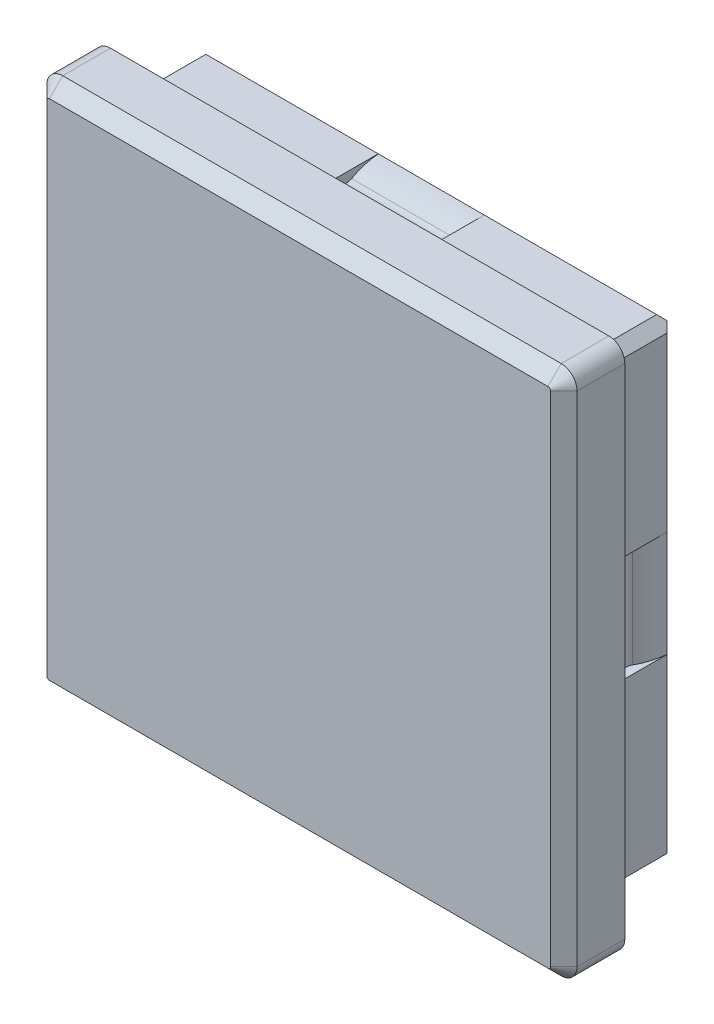
SolidWorks part; units mm, degrees
ref_plane "Front Plane" through (0, 0, 0) normal (1, 0, 0) x (0, 1, 0)
ref_plane "Top Plane" through (0, 0, 0) normal (0, 0, 1) x (0, 1, 0)
ref_plane "Right Plane" through (0, 0, 0) normal (0, 1, 0) x (-1, 0, 0)
ref_axis "center_axis-Z" through (0, 0, 210) along (0, 0, -1)
sketch "Sketch1" plane through (0, 0, 0) normal (0, 0, 1) x (0, 1, 0)
  line L1 (50, -50) -> (-50, -50)
  line L2 (50, -50) -> (50, 50)
  line L3 (50, 50) -> (-50, 50)
  line L4 (-50, -50) -> (-50, 50)
  line L5 (50, -50) -> (-50, 50) construction
  line L6 (50, 50) -> (-50, -50) construction
  line L7 (47, -47) -> (-47, -47)
  line L8 (47, -47) -> (47, 47)
  line L9 (47, 47) -> (-47, 47)
  line L10 (-47, -47) -> (-47, 47)
  line L11 (47, -47) -> (-47, 47) construction
  line L12 (47, 47) -> (-47, -47) construction
  point P0 (0, 0)
  point P6 (0, 0)
  dimension "D1" = 100
  dimension "D2" = 100
  dimension "D4" = 3
  dimension "D3" = 3
extrude "Boss-Extrude1" add sketch "Sketch1" along normal blind 25
fillet "Fillet1" radius 3 8 edges at (-47, 47, 12.5) (-47, -47, 12.5) (47, -47, 12.5) (47, 47, 12.5) (50, 50, 12.5) (-50, 50, 12.5) (-50, -50, 12.5) (50, -50, 12.5)
ref_plane "interface_plane" through (0, 0, 17.5) normal (0, 0, 1) x (0, 1, 0)
sketch "Sketch3" plane through (0, 0, 17.5) normal (0, 0, 1) x (0, 1, 0)
  line L0 (47, -50) -> (-47, -50)
  line L1 (47, -50) -> (-47, -50)
  line L2 (-50, -47) -> (-50, 47)
  line L3 (-50, -47) -> (-50, 47)
  line L4 (-47, 50) -> (47, 50)
  line L5 (-47, 50) -> (47, 50)
  line L6 (50, 47) -> (50, -47)
  line L7 (50, 47) -> (50, -47)
  arc A0 (47, -50) -> (50, -47) centre (47, -47) ccw
  arc A1 (47, -50) -> (50, -47) centre (47, -47) ccw
  arc A2 (-50, -47) -> (-47, -50) centre (-47, -47) ccw
  arc A3 (-50, -47) -> (-47, -50) centre (-47, -47) ccw
  arc A4 (-47, 50) -> (-50, 47) centre (-47, 47) ccw
  arc A5 (-47, 50) -> (-50, 47) centre (-47, 47) ccw
  arc A6 (50, 47) -> (47, 50) centre (47, 47) ccw
  arc A7 (50, 47) -> (47, 50) centre (47, 47) ccw
extrude "Boss-Extrude2" add sketch "Sketch3" against normal up to surface (17.5 mm away) up to face at (0, 0, 0)
sketch "Sketch4" plane through (0, 0, 0) normal (0, 0, -1) x (1, 0, 0)
  line L0 (47, -50) -> (-47, -50)
  line L1 (47, -50) -> (-47, -50)
  line L2 (-50, -47) -> (-50, 47)
  line L3 (-50, -47) -> (-50, 47)
  line L4 (-47, 50) -> (47, 50)
  line L5 (-47, 50) -> (47, 50)
  line L6 (50, 47) -> (50, -47)
  line L7 (50, 47) -> (50, -47)
  line L8 (-44.5, -42.5) -> (-44.5, 42.5)
  line L9 (-42.5, 44.5) -> (42.5, 44.5)
  line L10 (44.5, 42.5) -> (44.5, -42.5)
  line L11 (42.5, -44.5) -> (-42.5, -44.5)
  line L12 (-39.5, -39.5) -> (-39.5, 39.5)
  line L13 (-39.5, 39.5) -> (39.5, 39.5)
  line L14 (39.5, 39.5) -> (39.5, -39.5)
  line L15 (39.5, -39.5) -> (-39.5, -39.5)
  line L16 (-44.5, 44.5) -> (44.5, 44.5) construction
  line L17 (-44.5, -44.5) -> (-44.5, 44.5) construction
  line L18 (-44.5, 42.5) -> (-42.5, 44.5)
  line L19 (44.5, 44.5) -> (44.5, -44.5) construction
  line L20 (42.5, 44.5) -> (44.5, 42.5)
  line L21 (44.5, -44.5) -> (-44.5, -44.5) construction
  line L22 (44.5, -42.5) -> (42.5, -44.5)
  line L23 (-42.5, -44.5) -> (-44.5, -42.5)
  arc A0 (47, -50) -> (50, -47) centre (47, -47) ccw
  arc A1 (47, -50) -> (50, -47) centre (47, -47) ccw
  arc A2 (-50, -47) -> (-47, -50) centre (-47, -47) ccw
  arc A3 (-50, -47) -> (-47, -50) centre (-47, -47) ccw
  arc A4 (-47, 50) -> (-50, 47) centre (-47, 47) ccw
  arc A5 (-47, 50) -> (-50, 47) centre (-47, 47) ccw
  arc A6 (50, 47) -> (47, 50) centre (47, 47) ccw
  arc A7 (50, 47) -> (47, 50) centre (47, 47) ccw
  arc A12 (-39.5, 39.5) -> (-39.5, 39.5) centre (-39.5, 39.5) ccw
  arc A13 (39.5, 39.5) -> (39.5, 39.5) centre (39.5, 39.5) ccw
  arc A14 (39.5, -39.5) -> (39.5, -39.5) centre (39.5, -39.5) ccw
  arc A15 (-39.5, -39.5) -> (-39.5, -39.5) centre (-39.5, -39.5) ccw
  arc A16 (-44.5, 44.5) -> (-44.5, 44.5) centre (-44.5, 44.5) ccw construction
  arc A17 (44.5, 44.5) -> (44.5, 44.5) centre (44.5, 44.5) ccw construction
  arc A18 (44.5, -44.5) -> (44.5, -44.5) centre (44.5, -44.5) ccw construction
  arc A19 (-44.5, -44.5) -> (-44.5, -44.5) centre (-44.5, -44.5) ccw construction
  line M13 (-47, -50) -> (47, -50)
  arc M14 (47, -50) -> (50, -47) centre (47, -47) ccw
  line M15 (50, -47) -> (50, 47)
  arc M16 (50, 47) -> (47, 50) centre (47, 47) ccw
  line M17 (47, 50) -> (-47, 50)
  arc M18 (-47, 50) -> (-50, 47) centre (-47, 47) ccw
  line M19 (-50, 47) -> (-50, -47)
  arc M20 (-50, -47) -> (-47, -50) centre (-47, -47) ccw
  dimension "D3" = 2
  dimension "D4" = 2
  dimension "D1" = 89
  dimension "D5" = 2
  dimension "D6" = 2
  dimension "D7" = 2
  dimension "D8" = 2
  dimension "D9" = 2
  dimension "D10" = 2
  dimension "D2" = 5
extrude "Cut-Extrude2" cut sketch "Sketch4" against normal offset from surface (15.5 mm away) 2 contours L11 L23 L8 L18 L9 L20 L10 L22 M20 M13 M14 M15 M16 M17 M18 M19 region at (0, 48.5858, 0) up to plane "interface_plane"
extrude "Cut-Extrude3" cut sketch "Sketch4<3>" against normal up to surface (17.5 mm away) contours L15 L14 L13 L12 region at (0, 0, 0) up to plane "interface_plane"
sketch "Sketch4<3>" plane through (0, 0, 0) normal (0, 0, -1) x (1, 0, 0) same geometry as "Sketch4"
sketch "Sketch6" plane through (0, 0, 0) normal (0, 1, 0) x (-1, 0, 0)
  line L0 (47, 15.5) -> (-47, 15.5) construction
  line L1 (44.5, 15.5) -> (44.5, 0) construction
  circle A0 centre (44.7, 8) radius 2
  dimension "D1" = 4
  dimension "D2" = 7.5
  dimension "D3" = 0.2
extrude "Cut-Extrude4" cut sketch "Sketch6" against normal mid plane 20
fillet "Fillet3" radius 12 1 edges at (-44.5, 0, 6.01)
fillet "Fillet4" radius 2 1 edges at (-44.5, 0, 9.99)
pattern_circular "CirPattern3" count 4 over 360 about axis through (0, 0, 210) along (0, 0, -1) of "Cut-Extrude4", "Fillet3", "Fillet4"
chamfer "Chamfer2" distance 2 angle 45 4 edges at (-44.5, 0, 0) (0, -44.5, 0) (44.5, 0, 0) (0, 44.5, 0)
ref_plane "cap_intf" through (0, 0, 23) normal (0, 0, 1) x (0, -1, 0)
chamfer "Chamfer5" distance 3 angle 76 8 edges at (47, 0, 17.5) (46.1213, 46.1213, 17.5) (46.1213, -46.1213, 17.5) (0, 47, 17.5) (0, -47, 17.5) (-46.1213, 46.1213, 17.5) (-46.1213, -46.1213, 17.5) (-47, 0, 17.5) first distance on face at (0, 0, 17.5)
fillet "Fillet10" radius 17 4 edges at (0, 39.5, 17.5) (-39.5, 0, 17.5) (0, -39.5, 17.5) (39.5, 0, 17.5)
fillet "Fillet11" radius 3 8 edges at (-39.5, -39.5, 2.9891) (39.5, -39.5, 2.9891) (39.5, 39.5, 2.9891) (-39.5, 39.5, 2.9891) (-40.6649, -40.6649, 12.1629) (40.6649, -40.6649, 12.1629) (40.6649, 40.6649, 12.1629) (-40.6649, 40.6649, 12.1629)
sketch "Sketch16" plane through (0, 0, 25) normal (0, 0, 1) x (1, 0, 0)
  line L4 (50, -47) -> (50, 47)
  line L5 (47, 50) -> (-47, 50)
  line L6 (-50, 47) -> (-50, -47)
  line L7 (-47, -50) -> (47, -50)
  line L8 (50, -47) -> (50, 47)
  line L9 (47, 50) -> (-47, 50)
  line L10 (-50, 47) -> (-50, -47)
  line L11 (-47, -50) -> (47, -50)
  arc A4 (50, 47) -> (47, 50) centre (47, 47) ccw
  arc A5 (-47, 50) -> (-50, 47) centre (-47, 47) ccw
  arc A6 (-50, -47) -> (-47, -50) centre (-47, -47) ccw
  arc A7 (47, -50) -> (50, -47) centre (47, -47) ccw
  arc A8 (50, 47) -> (47, 50) centre (47, 47) ccw
  arc A9 (-47, 50) -> (-50, 47) centre (-47, 47) ccw
  arc A10 (-50, -47) -> (-47, -50) centre (-47, -47) ccw
  arc A11 (47, -50) -> (50, -47) centre (47, -47) ccw
  dimension "D1" = 0
extrude "Boss-Extrude3" add sketch "Sketch16" along normal blind 2
sketch "Sketch15" plane through (0, 81.2243, 25) normal (0, 0, -1) x (1, 0, 0)
  line L0 (-47, 81.2243) -> (47, 81.2243) construction
  line L3 (-14.85, 81.2243) -> (14.85, 81.2243) construction
  text T0 "<b>43300040_A</b>" font "Century Gothic" height 5
  point P3 (-47, 74.8917)
extrude "Cut-Extrude6" cut sketch "Sketch15" against normal blind 0.6
chamfer "Chamfer6" distance 2.5 angle 45 8 edges at (0, -50, 27) (49.1213, -49.1213, 27) (-49.1213, -49.1213, 27) (50, 0, 27) (-50, 0, 27) (49.1213, 49.1213, 27) (-49.1213, 49.1213, 27) (0, 50, 27)
equation "\"D3@Sketch1\"=\"D4@Sketch1\""
equation "\"D1@Sketch1\"=\"D2@Sketch1\""
